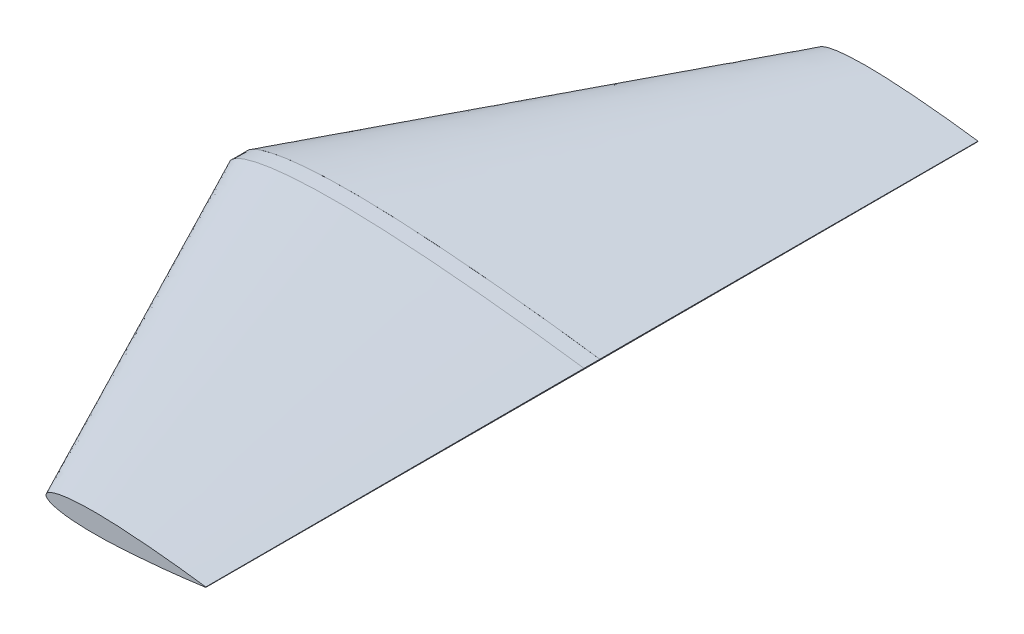
SolidWorks part; units mm, degrees
ref_plane "Front Plane" through (0, 0, 0) normal (0, 0, 1) x (1, 0, 0)
ref_plane "Top Plane" through (0, 0, 0) normal (0, 1, 0) x (1, 0, 0)
ref_plane "Right Plane" through (0, 0, 0) normal (1, 0, 0) x (0, 0, -1)
curve "Curve4"
  spline degree 3 poles (358.4, 0.4516, 0) (358.3705, 0.4558, 0) (358.2526, 0.4725, 0) (357.9874, 0.509, 0) (357.546, 0.5715, 0) (356.9284, 0.6576, 0) (356.1355, 0.7678, 0) (355.168, 0.9029, 0) (354.0268, 1.0605, 0) (352.7131, 1.2421, 0) (351.2282, 1.4459, 0) (349.5733, 1.6714, 0) (347.7504, 1.9192, 0) (345.7612, 2.1875, 0) (343.6077, 2.4759, 0) (341.2918, 2.7836, 0) (338.816, 3.1105, 0) (336.1826, 3.4545, 0) (333.3945, 3.8164, 0) (330.454, 4.1932, 0) (327.3643, 4.5866, 0) (324.1284, 4.9933, 0) (320.7495, 5.4142, 0) (317.231, 5.8471, 0) (313.5761, 6.2924, 0) (309.7885, 6.747, 0) (305.8722, 7.2123, 0) (301.8309, 7.6858, 0) (297.6686, 8.1675, 0) (293.3892, 8.6552, 0) (288.9974, 9.1496, 0) (284.497, 9.6477, 0) (279.8927, 10.1501, 0) (275.1891, 10.6553, 0) (270.3907, 11.1619, 0) (265.5024, 11.6693, 0) (260.5288, 12.1761, 0) (255.4751, 12.6823, 0) (250.346, 13.1852, 0) (245.1467, 13.6846, 0) (239.8823, 14.1796, 0) (234.5581, 14.668, 0) (229.1793, 15.1508, 0) (223.7512, 15.6241, 0) (218.2791, 16.0891, 0) (212.7683, 16.5431, 0) (207.2245, 16.9852, 0) (201.6529, 17.4146, 0) (196.0593, 17.8296, 0) (190.4489, 18.2291, 0) (184.8275, 18.6126, 0) (179.2006, 18.9767, 0) (173.5737, 19.3225, 0) (167.9523, 19.6472, 0) (162.3419, 19.9501, 0) (156.7482, 20.2303, 0) (151.1766, 20.4854, 0) (145.6328, 20.7154, 0) (140.1219, 20.9183, 0) (134.6497, 21.094, 0) (129.2216, 21.2398, 0) (123.8427, 21.3564, 0) (118.5184, 21.4415, 0) (113.2539, 21.4948, 0) (108.0545, 21.5157, 0) (102.9253, 21.5027, 0) (97.8714, 21.4558, 0) (92.8977, 21.3741, 0) (88.0093, 21.2574, 0) (83.2107, 21.1052, 0) (78.5069, 20.9172, 0) (73.9023, 20.6935, 0) (69.4018, 20.4334, 0) (65.0095, 20.1377, 0) (60.73, 19.8061, 0) (56.5673, 19.4392, 0) (52.5257, 19.0369, 0) (48.6089, 18.6007, 0) (44.821, 18.1299, 0) (41.1656, 17.6258, 0) (37.6465, 17.0894, 0) (34.2671, 16.5208, 0) (31.0305, 15.9218, 0) (27.9401, 15.2926, 0) (24.9987, 14.635, 0) (22.2095, 13.9494, 0) (19.5749, 13.2371, 0) (17.0977, 12.4992, 0) (14.7801, 11.737, 0) (12.6247, 10.9513, 0) (10.6329, 10.1436, 0) (8.807, 9.3144, 0) (7.1485, 8.4651, 0) (5.6585, 7.5971, 0) (4.3394, 6.7094, 0) (3.1907, 5.8047, 0) (2.2147, 4.8816, 0) (1.4118, 3.9406, 0) (0.7832, 2.9815, 0) (0.332, 2.0033, 0) (0.0601, 1.0072, 0) (-0.0298, 0, 0) (0.0601, -1.0072, 0) (0.332, -2.0033, 0) (0.7832, -2.9815, 0) (1.4118, -3.9406, 0) (2.2147, -4.8816, 0) (3.1907, -5.8047, 0) (4.3394, -6.7094, 0) (5.6585, -7.5971, 0) (7.1485, -8.4651, 0) (8.807, -9.3144, 0) (10.6329, -10.1436, 0) (12.6247, -10.9513, 0) (14.7801, -11.737, 0) (17.0977, -12.4992, 0) (19.5749, -13.2371, 0) (22.2095, -13.9494, 0) (24.9987, -14.635, 0) (27.9401, -15.2926, 0) (31.0305, -15.9218, 0) (34.2671, -16.5208, 0) (37.6465, -17.0894, 0) (41.1656, -17.6258, 0) (44.821, -18.1299, 0) (48.6089, -18.6007, 0) (52.5257, -19.0369, 0) (56.5673, -19.4392, 0) (60.73, -19.8061, 0) (65.0095, -20.1377, 0) (69.4018, -20.4334, 0) (73.9023, -20.6935, 0) (78.5069, -20.9172, 0) (83.2107, -21.1052, 0) (88.0093, -21.2574, 0) (92.8977, -21.3741, 0) (97.8714, -21.4558, 0) (102.9253, -21.5027, 0) (108.0545, -21.5157, 0) (113.2539, -21.4948, 0) (118.5184, -21.4415, 0) (123.8427, -21.3564, 0) (129.2216, -21.2398, 0) (134.6497, -21.094, 0) (140.1219, -20.9183, 0) (145.6328, -20.7154, 0) (151.1766, -20.4854, 0) (156.7482, -20.2303, 0) (162.3419, -19.9501, 0) (167.9523, -19.6472, 0) (173.5737, -19.3225, 0) (179.2006, -18.9767, 0) (184.8275, -18.6126, 0) (190.4489, -18.2291, 0) (196.0593, -17.8296, 0) (201.6529, -17.4146, 0) (207.2245, -16.9852, 0) (212.7683, -16.5431, 0) (218.2791, -16.0891, 0) (223.7512, -15.6241, 0) (229.1793, -15.1508, 0) (234.5581, -14.668, 0) (239.8823, -14.1796, 0) (245.1467, -13.6846, 0) (250.346, -13.1852, 0) (255.4751, -12.6823, 0) (260.5288, -12.1761, 0) (265.5024, -11.6693, 0) (270.3907, -11.1619, 0) (275.1891, -10.6553, 0) (279.8927, -10.1501, 0) (284.497, -9.6477, 0) (288.9974, -9.1496, 0) (293.3892, -8.6552, 0) (297.6686, -8.1675, 0) (301.8309, -7.6858, 0) (305.8722, -7.2123, 0) (309.7885, -6.747, 0) (313.5761, -6.2924, 0) (317.231, -5.8471, 0) (320.7495, -5.4142, 0) (324.1284, -4.9933, 0) (327.3643, -4.5866, 0) (330.454, -4.1932, 0) (333.3945, -3.8164, 0) (336.1826, -3.4545, 0) (338.816, -3.1105, 0) (341.2918, -2.7836, 0) (343.6077, -2.4759, 0) (345.7612, -2.1875, 0) (347.7504, -1.9192, 0) (349.5733, -1.6714, 0) (351.2282, -1.4459, 0) (352.7131, -1.2421, 0) (354.0268, -1.0605, 0) (355.168, -0.9029, 0) (356.1355, -0.7678, 0) (356.9284, -0.6576, 0) (357.546, -0.5715, 0) (357.9874, -0.509, 0) (358.2526, -0.4725, 0) (358.3705, -0.4558, 0) (358.4, -0.4516, 0) knots 0 0 0 0 0.000122 0.000489 0.001099 0.001952 0.003048 0.004385 0.005962 0.007777 0.009829 0.012115 0.014633 0.01738 0.020354 0.023551 0.02697 0.030605 0.034453 0.03851 0.042773 0.047237 0.051897 0.05675 0.061789 0.067011 0.072409 0.077978 0.083713 0.089608 0.095657 0.101854 0.108194 0.114669 0.121273 0.127999 0.134842 0.141793 0.148847 0.155997 0.163234 0.170552 0.177943 0.185401 0.192918 0.200486 0.208098 0.215746 0.223423 0.231122 0.238834 0.246551 0.254267 0.261974 0.269664 0.27733 0.284963 0.292558 0.300106 0.307599 0.315032 0.322395 0.329684 0.336889 0.344006 0.351026 0.357943 0.364751 0.371444 0.378015 0.384458 0.390767 0.396937 0.402962 0.408837 0.414556 0.420115 0.425508 0.430733 0.435783 0.440655 0.445344 0.449849 0.454165 0.458289 0.462219 0.465954 0.469491 0.472828 0.475967 0.478906 0.481648 0.484196 0.486552 0.488722 0.490717 0.492547 0.494228 0.495783 0.497239 0.498632 0.5 0.501368 0.502761 0.504217 0.505772 0.507453 0.509283 0.511278 0.513448 0.515804 0.518352 0.521094 0.524033 0.527172 0.530509 0.534046 0.537781 0.541711 0.545835 0.550151 0.554656 0.559345 0.564217 0.569267 0.574492 0.579885 0.585444 0.591163 0.597038 0.603063 0.609233 0.615542 0.621985 0.628556 0.635249 0.642057 0.648974 0.655994 0.663111 0.670316 0.677605 0.684968 0.692401 0.699894 0.707442 0.715037 0.72267 0.730336 0.738026 0.745733 0.753449 0.761166 0.768878 0.776577 0.784254 0.791902 0.799514 0.807082 0.814599 0.822057 0.829448 0.836766 0.844003 0.851153 0.858207 0.865158 0.872001 0.878727 0.885331 0.891806 0.898146 0.904343 0.910392 0.916287 0.922022 0.927591 0.932989 0.938211 0.94325 0.948103 0.952763 0.957227 0.96149 0.965547 0.969395 0.97303 0.976449 0.979646 0.98262 0.985367 0.987885 0.990171 0.992223 0.994038 0.995615 0.996952 0.998048 0.998901 0.999511 0.999878 1 1 1 1
sketch "Sketch2" plane through (0, 0, 0) normal (0, 0, 1) x (1, 0, 0)
  line L0 (358.4, 0.4516) -> (358.4, -0.4516)
  spline S0 degree 3 poles (958.0339, 3953.6087) (386.4418, -11.6955) (372.8591, -1.5368) (357.9874, 0.509) (357.546, 0.5715) (356.9284, 0.6576) (356.1355, 0.7678) (355.168, 0.9029) (354.0268, 1.0605) (352.7131, 1.2421) (351.2282, 1.4459) (349.5733, 1.6714) (347.7504, 1.9192) (345.7612, 2.1875) (343.6077, 2.4759) (341.2918, 2.7836) (338.816, 3.1105) (336.1826, 3.4545) (333.3945, 3.8164) (330.454, 4.1932) (327.3643, 4.5866) (324.1284, 4.9933) (320.7495, 5.4142) (317.231, 5.8471) (313.5761, 6.2924) (309.7885, 6.747) (305.8722, 7.2123) (301.8309, 7.6858) (297.6686, 8.1675) (293.3892, 8.6552) (288.9974, 9.1496) (284.497, 9.6477) (279.8927, 10.1501) (275.1891, 10.6553) (270.3907, 11.1619) (265.5024, 11.6693) (260.5288, 12.1761) (255.4751, 12.6823) (250.346, 13.1852) (245.1467, 13.6846) (239.8823, 14.1796) (234.5581, 14.668) (229.1793, 15.1508) (223.7512, 15.6241) (218.2791, 16.0891) (212.7683, 16.5431) (207.2245, 16.9852) (201.6529, 17.4146) (196.0593, 17.8296) (190.4489, 18.2291) (184.8275, 18.6126) (179.2006, 18.9767) (173.5737, 19.3225) (167.9523, 19.6472) (162.3419, 19.9501) (156.7482, 20.2303) (151.1766, 20.4854) (145.6328, 20.7154) (140.1219, 20.9183) (134.6497, 21.094) (129.2216, 21.2398) (123.8427, 21.3564) (118.5184, 21.4415) (113.2539, 21.4948) (108.0545, 21.5157) (102.9253, 21.5027) (97.8714, 21.4558) (92.8977, 21.3741) (88.0093, 21.2574) (83.2107, 21.1052) (78.5069, 20.9172) (73.9023, 20.6935) (69.4018, 20.4334) (65.0095, 20.1377) (60.73, 19.8061) (56.5673, 19.4392) (52.5257, 19.0369) (48.6089, 18.6007) (44.821, 18.1299) (41.1656, 17.6258) (37.6465, 17.0894) (34.2671, 16.5208) (31.0305, 15.9218) (27.9401, 15.2926) (24.9987, 14.635) (22.2095, 13.9494) (19.5749, 13.2371) (17.0977, 12.4992) (14.7801, 11.737) (12.6247, 10.9513) (10.6329, 10.1436) (8.807, 9.3144) (7.1485, 8.4651) (5.6585, 7.5971) (4.3394, 6.7094) (3.1907, 5.8047) (2.2147, 4.8816) (1.4118, 3.9406) (0.7832, 2.9815) (0.332, 2.0033) (0.0601, 1.0072) (-0.0298, 0) (0.0601, -1.0072) (0.332, -2.0033) (0.7832, -2.9815) (1.4118, -3.9406) (2.2147, -4.8816) (3.1907, -5.8047) (4.3394, -6.7094) (5.6585, -7.5971) (7.1485, -8.4651) (8.807, -9.3144) (10.6329, -10.1436) (12.6247, -10.9513) (14.7801, -11.737) (17.0977, -12.4992) (19.5749, -13.2371) (22.2095, -13.9494) (24.9987, -14.635) (27.9401, -15.2926) (31.0305, -15.9218) (34.2671, -16.5208) (37.6465, -17.0894) (41.1656, -17.6258) (44.821, -18.1299) (48.6089, -18.6007) (52.5257, -19.0369) (56.5673, -19.4392) (60.73, -19.8061) (65.0095, -20.1377) (69.4018, -20.4334) (73.9023, -20.6935) (78.5069, -20.9172) (83.2107, -21.1052) (88.0093, -21.2574) (92.8977, -21.3741) (97.8714, -21.4558) (102.9253, -21.5027) (108.0545, -21.5157) (113.2539, -21.4948) (118.5184, -21.4415) (123.8427, -21.3564) (129.2216, -21.2398) (134.6497, -21.094) (140.1219, -20.9183) (145.6328, -20.7154) (151.1766, -20.4854) (156.7482, -20.2303) (162.3419, -19.9501) (167.9523, -19.6472) (173.5737, -19.3225) (179.2006, -18.9767) (184.8275, -18.6126) (190.4489, -18.2291) (196.0593, -17.8296) (201.6529, -17.4146) (207.2245, -16.9852) (212.7683, -16.5431) (218.2791, -16.0891) (223.7512, -15.6241) (229.1793, -15.1508) (234.5581, -14.668) (239.8823, -14.1796) (245.1467, -13.6846) (250.346, -13.1852) (255.4751, -12.6823) (260.5288, -12.1761) (265.5024, -11.6693) (270.3907, -11.1619) (275.1891, -10.6553) (279.8927, -10.1501) (284.497, -9.6477) (288.9974, -9.1496) (293.3892, -8.6552) (297.6686, -8.1675) (301.8309, -7.6858) (305.8722, -7.2123) (309.7885, -6.747) (313.5761, -6.2924) (317.231, -5.8471) (320.7495, -5.4142) (324.1284, -4.9933) (327.3643, -4.5866) (330.454, -4.1932) (333.3945, -3.8164) (336.1826, -3.4545) (338.816, -3.1105) (341.2918, -2.7836) (343.6077, -2.4759) (345.7612, -2.1875) (347.7504, -1.9192) (349.5733, -1.6714) (351.2282, -1.4459) (352.7131, -1.2421) (354.0268, -1.0605) (355.168, -0.9029) (356.1355, -0.7678) (356.9284, -0.6576) (357.546, -0.5715) (357.9874, -0.509) (372.8587, 1.5367) (386.441, 11.6949) (957.9815, -3953.2445) knots -0.060521 -0.060521 -0.060521 -0.060521 0.000122 0.000489 0.001099 0.001952 0.003048 0.004385 0.005962 0.007777 0.009829 0.012115 0.014633 0.01738 0.020354 0.023551 0.02697 0.030605 0.034453 0.03851 0.042773 0.047237 0.051897 0.05675 0.061789 0.067011 0.072409 0.077978 0.083713 0.089608 0.095657 0.101854 0.108194 0.114669 0.121273 0.127999 0.134842 0.141793 0.148847 0.155997 0.163234 0.170552 0.177943 0.185401 0.192918 0.200486 0.208098 0.215746 0.223423 0.231122 0.238834 0.246551 0.254267 0.261974 0.269664 0.27733 0.284963 0.292558 0.300106 0.307599 0.315032 0.322395 0.329684 0.336889 0.344006 0.351026 0.357943 0.364751 0.371444 0.378015 0.384458 0.390767 0.396937 0.402962 0.408837 0.414556 0.420115 0.425508 0.430733 0.435783 0.440655 0.445344 0.449849 0.454165 0.458289 0.462219 0.465954 0.469491 0.472828 0.475967 0.478906 0.481648 0.484196 0.486552 0.488722 0.490717 0.492547 0.494228 0.495783 0.497239 0.498632 0.5 0.501368 0.502761 0.504217 0.505772 0.507453 0.509283 0.511278 0.513448 0.515804 0.518352 0.521094 0.524033 0.527172 0.530509 0.534046 0.537781 0.541711 0.545835 0.550151 0.554656 0.559345 0.564217 0.569267 0.574492 0.579885 0.585444 0.591163 0.597038 0.603063 0.609233 0.615542 0.621985 0.628556 0.635249 0.642057 0.648974 0.655994 0.663111 0.670316 0.677605 0.684968 0.692401 0.699894 0.707442 0.715037 0.72267 0.730336 0.738026 0.745733 0.753449 0.761166 0.768878 0.776577 0.784254 0.791902 0.799514 0.807082 0.814599 0.822057 0.829448 0.836766 0.844003 0.851153 0.858207 0.865158 0.872001 0.878727 0.885331 0.891806 0.898146 0.904343 0.910392 0.916287 0.922022 0.927591 0.932989 0.938211 0.94325 0.948103 0.952763 0.957227 0.96149 0.965547 0.969395 0.97303 0.976449 0.979646 0.98262 0.985367 0.987885 0.990171 0.992223 0.994038 0.995615 0.996952 0.998048 0.998901 0.999511 0.999878 1.060519 1.060519 1.060519 1.060519 only from (358.4, 0.4516) to (358.4, -0.4516) construction
  spline S1 degree 3 poles (358.4, 0.4516) (358.3705, 0.4558) (358.2526, 0.4725) (357.9874, 0.509) (357.546, 0.5715) (356.9284, 0.6576) (356.1355, 0.7678) (355.168, 0.9029) (354.0268, 1.0605) (352.7131, 1.2421) (351.2282, 1.4459) (349.5733, 1.6714) (347.7504, 1.9192) (345.7612, 2.1875) (343.6077, 2.4759) (341.2918, 2.7836) (338.816, 3.1105) (336.1826, 3.4545) (333.3945, 3.8164) (330.454, 4.1932) (327.3643, 4.5866) (324.1284, 4.9933) (320.7495, 5.4142) (317.231, 5.8471) (313.5761, 6.2924) (309.7885, 6.747) (305.8722, 7.2123) (301.8309, 7.6858) (297.6686, 8.1675) (293.3892, 8.6552) (288.9974, 9.1496) (284.497, 9.6477) (279.8927, 10.1501) (275.1891, 10.6553) (270.3907, 11.1619) (265.5024, 11.6693) (260.5288, 12.1761) (255.4751, 12.6823) (250.346, 13.1852) (245.1467, 13.6846) (239.8823, 14.1796) (234.5581, 14.668) (229.1793, 15.1508) (223.7512, 15.6241) (218.2791, 16.0891) (212.7683, 16.5431) (207.2245, 16.9852) (201.6529, 17.4146) (196.0593, 17.8296) (190.4489, 18.2291) (184.8275, 18.6126) (179.2006, 18.9767) (173.5737, 19.3225) (167.9523, 19.6472) (162.3419, 19.9501) (156.7482, 20.2303) (151.1766, 20.4854) (145.6328, 20.7154) (140.1219, 20.9183) (134.6497, 21.094) (129.2216, 21.2398) (123.8427, 21.3564) (118.5184, 21.4415) (113.2539, 21.4948) (108.0545, 21.5157) (102.9253, 21.5027) (97.8714, 21.4558) (92.8977, 21.3741) (88.0093, 21.2574) (83.2107, 21.1052) (78.5069, 20.9172) (73.9023, 20.6935) (69.4018, 20.4334) (65.0095, 20.1377) (60.73, 19.8061) (56.5673, 19.4392) (52.5257, 19.0369) (48.6089, 18.6007) (44.821, 18.1299) (41.1656, 17.6258) (37.6465, 17.0894) (34.2671, 16.5208) (31.0305, 15.9218) (27.9401, 15.2926) (24.9987, 14.635) (22.2095, 13.9494) (19.5749, 13.2371) (17.0977, 12.4992) (14.7801, 11.737) (12.6247, 10.9513) (10.6329, 10.1436) (8.807, 9.3144) (7.1485, 8.4651) (5.6585, 7.5971) (4.3394, 6.7094) (3.1907, 5.8047) (2.2147, 4.8816) (1.4118, 3.9406) (0.7832, 2.9815) (0.332, 2.0033) (0.0601, 1.0072) (-0.0298, 0) (0.0601, -1.0072) (0.332, -2.0033) (0.7832, -2.9815) (1.4118, -3.9406) (2.2147, -4.8816) (3.1907, -5.8047) (4.3394, -6.7094) (5.6585, -7.5971) (7.1485, -8.4651) (8.807, -9.3144) (10.6329, -10.1436) (12.6247, -10.9513) (14.7801, -11.737) (17.0977, -12.4992) (19.5749, -13.2371) (22.2095, -13.9494) (24.9987, -14.635) (27.9401, -15.2926) (31.0305, -15.9218) (34.2671, -16.5208) (37.6465, -17.0894) (41.1656, -17.6258) (44.821, -18.1299) (48.6089, -18.6007) (52.5257, -19.0369) (56.5673, -19.4392) (60.73, -19.8061) (65.0095, -20.1377) (69.4018, -20.4334) (73.9023, -20.6935) (78.5069, -20.9172) (83.2107, -21.1052) (88.0093, -21.2574) (92.8977, -21.3741) (97.8714, -21.4558) (102.9253, -21.5027) (108.0545, -21.5157) (113.2539, -21.4948) (118.5184, -21.4415) (123.8427, -21.3564) (129.2216, -21.2398) (134.6497, -21.094) (140.1219, -20.9183) (145.6328, -20.7154) (151.1766, -20.4854) (156.7482, -20.2303) (162.3419, -19.9501) (167.9523, -19.6472) (173.5737, -19.3225) (179.2006, -18.9767) (184.8275, -18.6126) (190.4489, -18.2291) (196.0593, -17.8296) (201.6529, -17.4146) (207.2245, -16.9852) (212.7683, -16.5431) (218.2791, -16.0891) (223.7512, -15.6241) (229.1793, -15.1508) (234.5581, -14.668) (239.8823, -14.1796) (245.1467, -13.6846) (250.346, -13.1852) (255.4751, -12.6823) (260.5288, -12.1761) (265.5024, -11.6693) (270.3907, -11.1619) (275.1891, -10.6553) (279.8927, -10.1501) (284.497, -9.6477) (288.9974, -9.1496) (293.3892, -8.6552) (297.6686, -8.1675) (301.8309, -7.6858) (305.8722, -7.2123) (309.7885, -6.747) (313.5761, -6.2924) (317.231, -5.8471) (320.7495, -5.4142) (324.1284, -4.9933) (327.3643, -4.5866) (330.454, -4.1932) (333.3945, -3.8164) (336.1826, -3.4545) (338.816, -3.1105) (341.2918, -2.7836) (343.6077, -2.4759) (345.7612, -2.1875) (347.7504, -1.9192) (349.5733, -1.6714) (351.2282, -1.4459) (352.7131, -1.2421) (354.0268, -1.0605) (355.168, -0.9029) (356.1355, -0.7678) (356.9284, -0.6576) (357.546, -0.5715) (357.9874, -0.509) (358.2526, -0.4725) (358.3705, -0.4558) (358.4, -0.4516) knots 0 0 0 0 0.000122 0.000489 0.001099 0.001952 0.003048 0.004385 0.005962 0.007777 0.009829 0.012115 0.014633 0.01738 0.020354 0.023551 0.02697 0.030605 0.034453 0.03851 0.042773 0.047237 0.051897 0.05675 0.061789 0.067011 0.072409 0.077978 0.083713 0.089608 0.095657 0.101854 0.108194 0.114669 0.121273 0.127999 0.134842 0.141793 0.148847 0.155997 0.163234 0.170552 0.177943 0.185401 0.192918 0.200486 0.208098 0.215746 0.223423 0.231122 0.238834 0.246551 0.254267 0.261974 0.269664 0.27733 0.284963 0.292558 0.300106 0.307599 0.315032 0.322395 0.329684 0.336889 0.344006 0.351026 0.357943 0.364751 0.371444 0.378015 0.384458 0.390767 0.396937 0.402962 0.408837 0.414556 0.420115 0.425508 0.430733 0.435783 0.440655 0.445344 0.449849 0.454165 0.458289 0.462219 0.465954 0.469491 0.472828 0.475967 0.478906 0.481648 0.484196 0.486552 0.488722 0.490717 0.492547 0.494228 0.495783 0.497239 0.498632 0.5 0.501368 0.502761 0.504217 0.505772 0.507453 0.509283 0.511278 0.513448 0.515804 0.518352 0.521094 0.524033 0.527172 0.530509 0.534046 0.537781 0.541711 0.545835 0.550151 0.554656 0.559345 0.564217 0.569267 0.574492 0.579885 0.585444 0.591163 0.597038 0.603063 0.609233 0.615542 0.621985 0.628556 0.635249 0.642057 0.648974 0.655994 0.663111 0.670316 0.677605 0.684968 0.692401 0.699894 0.707442 0.715037 0.72267 0.730336 0.738026 0.745733 0.753449 0.761166 0.768878 0.776577 0.784254 0.791902 0.799514 0.807082 0.814599 0.822057 0.829448 0.836766 0.844003 0.851153 0.858207 0.865158 0.872001 0.878727 0.885331 0.891806 0.898146 0.904343 0.910392 0.916287 0.922022 0.927591 0.932989 0.938211 0.94325 0.948103 0.952763 0.957227 0.96149 0.965547 0.969395 0.97303 0.976449 0.979646 0.98262 0.985367 0.987885 0.990171 0.992223 0.994038 0.995615 0.996952 0.998048 0.998901 0.999511 0.999878 1 1 1 1
  point P2 (358.4, 0)
ref_plane "Plane1" through (0, 0, 382.02) normal (0, 0, 1) x (1, 0, 0)
curve "Curve6"
  spline degree 3 poles (161, 0.2, 0) (160.9167, 0.2136, 0) (160.5878, 0.2674, 0) (159.8459, 0.3582, 0) (158.6167, 0.5336, 0) (156.9044, 0.7747, 0) (154.7197, 1.0579, 0) (152.0808, 1.4127, 0) (149, 1.8068, 0) (145.495, 2.263, 0) (141.5867, 2.7335, 0) (137.3047, 3.2584, 0) (132.6749, 3.797, 0) (127.7205, 4.3416, 0) (122.4781, 4.9135, 0) (116.9751, 5.4844, 0) (111.2473, 6.0363, 0) (105.3289, 6.6051, 0) (99.2544, 7.1256, 0) (93.0685, 7.6401, 0) (86.8052, 8.1104, 0) (80.5015, 8.5276, 0) (74.1982, 8.8988, 0) (67.9348, 9.2091, 0) (61.7481, 9.4549, 0) (55.674, 9.6008, 0) (49.7536, 9.6736, 0) (44.0259, 9.6622, 0) (38.5218, 9.5268, 0) (33.277, 9.3152, 0) (28.3219, 8.9982, 0) (23.6896, 8.584, 0) (19.4031, 8.0712, 0) (15.4933, 7.4578, 0) (11.9838, 6.7608, 0) (8.8904, 6.0144, 0) (6.2467, 5.1543, 0) (4.043, 4.2646, 0) (2.2931, 3.3144, 0) (1.0207, 2.2893, 0) (0.197, 1.1962, 0) (-0.0922, 0, 0) (0.197, -1.1962, 0) (1.0207, -2.2893, 0) (2.2931, -3.3144, 0) (4.043, -4.2646, 0) (6.2467, -5.1543, 0) (8.8904, -6.0144, 0) (11.9838, -6.7608, 0) (15.4933, -7.4578, 0) (19.4031, -8.0712, 0) (23.6896, -8.584, 0) (28.3219, -8.9982, 0) (33.277, -9.3152, 0) (38.5218, -9.5268, 0) (44.0259, -9.6622, 0) (49.7536, -9.6736, 0) (55.674, -9.6008, 0) (61.7481, -9.4549, 0) (67.9348, -9.2091, 0) (74.1982, -8.8988, 0) (80.5015, -8.5276, 0) (86.8052, -8.1104, 0) (93.0685, -7.6401, 0) (99.2544, -7.1256, 0) (105.3289, -6.6051, 0) (111.2473, -6.0363, 0) (116.9751, -5.4844, 0) (122.4781, -4.9135, 0) (127.7205, -4.3416, 0) (132.6749, -3.797, 0) (137.3047, -3.2584, 0) (141.5867, -2.7335, 0) (145.495, -2.263, 0) (149, -1.8068, 0) (152.0808, -1.4127, 0) (154.7197, -1.0579, 0) (156.9044, -0.7747, 0) (158.6167, -0.5336, 0) (159.8459, -0.3582, 0) (160.5878, -0.2674, 0) (160.9167, -0.2136, 0) (161, -0.2, 0) knots 0 0 0 0 0.000771 0.003046 0.006828 0.012119 0.018848 0.02696 0.036452 0.047231 0.059262 0.072425 0.086655 0.101857 0.117974 0.134848 0.152416 0.17056 0.189182 0.208132 0.227285 0.24658 0.265865 0.284988 0.303888 0.322445 0.340511 0.357996 0.374785 0.390822 0.405963 0.420155 0.433319 0.445408 0.456311 0.466012 0.47447 0.481694 0.487709 0.492596 0.496534 0.5 0.503466 0.507404 0.512291 0.518306 0.52553 0.533988 0.543689 0.554592 0.566681 0.579845 0.594037 0.609178 0.625215 0.642004 0.659489 0.677555 0.696112 0.715012 0.734135 0.75342 0.772715 0.791868 0.810818 0.82944 0.847584 0.865152 0.882026 0.898143 0.913345 0.927575 0.940738 0.952769 0.963548 0.97304 0.981152 0.987881 0.993172 0.996954 0.999229 1 1 1 1
sketch "Sketch3" plane through (0, 0, 0) normal (0, 0, 1) x (1, 0, 0)
  line L0 (161, 0.2) -> (161, -0.2)
  spline S0 degree 3 poles (485.6143, 1973.3383) (180.7866, -18.3284) (171.6884, -1.0915) (159.8459, 0.3582) (158.6167, 0.5336) (156.9044, 0.7747) (154.7197, 1.0579) (152.0808, 1.4127) (149, 1.8068) (145.495, 2.263) (141.5867, 2.7335) (137.3047, 3.2584) (132.6749, 3.797) (127.7205, 4.3416) (122.4781, 4.9135) (116.9751, 5.4844) (111.2473, 6.0363) (105.3289, 6.6051) (99.2544, 7.1256) (93.0685, 7.6401) (86.8052, 8.1104) (80.5015, 8.5276) (74.1982, 8.8988) (67.9348, 9.2091) (61.7481, 9.4549) (55.674, 9.6008) (49.7536, 9.6736) (44.0259, 9.6622) (38.5218, 9.5268) (33.277, 9.3152) (28.3219, 8.9982) (23.6896, 8.584) (19.4031, 8.0712) (15.4933, 7.4578) (11.9838, 6.7608) (8.8904, 6.0144) (6.2467, 5.1543) (4.043, 4.2646) (2.2931, 3.3144) (1.0207, 2.2893) (0.197, 1.1962) (-0.0922, 0) (0.197, -1.1962) (1.0207, -2.2893) (2.2931, -3.3144) (4.043, -4.2646) (6.2467, -5.1543) (8.8904, -6.0144) (11.9838, -6.7608) (15.4933, -7.4578) (19.4031, -8.0712) (23.6896, -8.584) (28.3219, -8.9982) (33.277, -9.3152) (38.5218, -9.5268) (44.0259, -9.6622) (49.7536, -9.6736) (55.674, -9.6008) (61.7481, -9.4549) (67.9348, -9.2091) (74.1982, -8.8988) (80.5015, -8.5276) (86.8052, -8.1104) (93.0685, -7.6401) (99.2544, -7.1256) (105.3289, -6.6051) (111.2473, -6.0363) (116.9751, -5.4844) (122.4781, -4.9135) (127.7205, -4.3416) (132.6749, -3.797) (137.3047, -3.2584) (141.5867, -2.7335) (145.495, -2.263) (149, -1.8068) (152.0808, -1.4127) (154.7197, -1.0579) (156.9044, -0.7747) (158.6167, -0.5336) (159.8459, -0.3582) (171.6881, 1.0915) (180.7861, 18.3274) (485.5887, -1973.1705) knots -0.102179 -0.102179 -0.102179 -0.102179 0.000771 0.003046 0.006828 0.012119 0.018848 0.02696 0.036452 0.047231 0.059262 0.072425 0.086655 0.101857 0.117974 0.134848 0.152416 0.17056 0.189182 0.208132 0.227285 0.24658 0.265865 0.284988 0.303888 0.322445 0.340511 0.357996 0.374785 0.390822 0.405963 0.420155 0.433319 0.445408 0.456311 0.466012 0.47447 0.481694 0.487709 0.492596 0.496534 0.5 0.503466 0.507404 0.512291 0.518306 0.52553 0.533988 0.543689 0.554592 0.566681 0.579845 0.594037 0.609178 0.625215 0.642004 0.659489 0.677555 0.696112 0.715012 0.734135 0.75342 0.772715 0.791868 0.810818 0.82944 0.847584 0.865152 0.882026 0.898143 0.913345 0.927575 0.940738 0.952769 0.963548 0.97304 0.981152 0.987881 0.993172 0.996954 0.999229 1.102176 1.102176 1.102176 1.102176 only from (161, 0.2) to (161, -0.2) construction
  spline S1 degree 3 poles (161, 0.2) (160.9167, 0.2136) (160.5878, 0.2674) (159.8459, 0.3582) (158.6167, 0.5336) (156.9044, 0.7747) (154.7197, 1.0579) (152.0808, 1.4127) (149, 1.8068) (145.495, 2.263) (141.5867, 2.7335) (137.3047, 3.2584) (132.6749, 3.797) (127.7205, 4.3416) (122.4781, 4.9135) (116.9751, 5.4844) (111.2473, 6.0363) (105.3289, 6.6051) (99.2544, 7.1256) (93.0685, 7.6401) (86.8052, 8.1104) (80.5015, 8.5276) (74.1982, 8.8988) (67.9348, 9.2091) (61.7481, 9.4549) (55.674, 9.6008) (49.7536, 9.6736) (44.0259, 9.6622) (38.5218, 9.5268) (33.277, 9.3152) (28.3219, 8.9982) (23.6896, 8.584) (19.4031, 8.0712) (15.4933, 7.4578) (11.9838, 6.7608) (8.8904, 6.0144) (6.2467, 5.1543) (4.043, 4.2646) (2.2931, 3.3144) (1.0207, 2.2893) (0.197, 1.1962) (-0.0922, 0) (0.197, -1.1962) (1.0207, -2.2893) (2.2931, -3.3144) (4.043, -4.2646) (6.2467, -5.1543) (8.8904, -6.0144) (11.9838, -6.7608) (15.4933, -7.4578) (19.4031, -8.0712) (23.6896, -8.584) (28.3219, -8.9982) (33.277, -9.3152) (38.5218, -9.5268) (44.0259, -9.6622) (49.7536, -9.6736) (55.674, -9.6008) (61.7481, -9.4549) (67.9348, -9.2091) (74.1982, -8.8988) (80.5015, -8.5276) (86.8052, -8.1104) (93.0685, -7.6401) (99.2544, -7.1256) (105.3289, -6.6051) (111.2473, -6.0363) (116.9751, -5.4844) (122.4781, -4.9135) (127.7205, -4.3416) (132.6749, -3.797) (137.3047, -3.2584) (141.5867, -2.7335) (145.495, -2.263) (149, -1.8068) (152.0808, -1.4127) (154.7197, -1.0579) (156.9044, -0.7747) (158.6167, -0.5336) (159.8459, -0.3582) (160.5878, -0.2674) (160.9167, -0.2136) (161, -0.2) knots 0 0 0 0 0.000771 0.003046 0.006828 0.012119 0.018848 0.02696 0.036452 0.047231 0.059262 0.072425 0.086655 0.101857 0.117974 0.134848 0.152416 0.17056 0.189182 0.208132 0.227285 0.24658 0.265865 0.284988 0.303888 0.322445 0.340511 0.357996 0.374785 0.390822 0.405963 0.420155 0.433319 0.445408 0.456311 0.466012 0.47447 0.481694 0.487709 0.492596 0.496534 0.5 0.503466 0.507404 0.512291 0.518306 0.52553 0.533988 0.543689 0.554592 0.566681 0.579845 0.594037 0.609178 0.625215 0.642004 0.659489 0.677555 0.696112 0.715012 0.734135 0.75342 0.772715 0.791868 0.810818 0.82944 0.847584 0.865152 0.882026 0.898143 0.913345 0.927575 0.940738 0.952769 0.963548 0.97304 0.981152 0.987881 0.993172 0.996954 0.999229 1 1 1 1
sketch "Sketch4" plane through (0, 0, 382.02) normal (0, 0, 1) x (1, 0, 0)
  line L0 (358.4, 0.2005) -> (358.4, -0.2005)
  spline S1 degree 3 poles (358.4, 0.2005) (358.3165, 0.2142) (357.9867, 0.2681) (357.243, 0.3591) (356.0106, 0.535) (354.2939, 0.7767) (352.1036, 1.0606) (349.4579, 1.4163) (346.3693, 1.8115) (342.8552, 2.2688) (338.9369, 2.7405) (334.644, 3.2668) (330.0023, 3.8068) (325.0353, 4.3527) (319.7794, 4.9261) (314.2623, 5.4985) (308.5198, 6.0517) (302.5863, 6.622) (296.4961, 7.1438) (290.2944, 7.6597) (284.0151, 8.1312) (277.6952, 8.5494) (271.3758, 8.9216) (265.0963, 9.2327) (258.8938, 9.4791) (252.8041, 9.6254) (246.8685, 9.6983) (241.1261, 9.687) (235.6079, 9.5512) (230.3497, 9.3391) (225.3819, 9.0213) (220.7378, 8.606) (216.4402, 8.0918) (212.5205, 7.4769) (209.002, 6.7781) (205.9006, 6.0298) (203.2501, 5.1675) (201.0408, 4.2755) (199.2864, 3.3229) (198.0108, 2.2952) (197.1849, 1.1993) (196.895, 0) (197.1849, -1.1993) (198.0108, -2.2952) (199.2864, -3.3229) (201.0408, -4.2755) (203.2501, -5.1675) (205.9006, -6.0298) (209.002, -6.7781) (212.5205, -7.4769) (216.4402, -8.0918) (220.7378, -8.606) (225.3819, -9.0213) (230.3497, -9.3391) (235.6079, -9.5512) (241.1261, -9.687) (246.8685, -9.6983) (252.8041, -9.6254) (258.8938, -9.4791) (265.0963, -9.2327) (271.3758, -8.9216) (277.6952, -8.5494) (284.0151, -8.1312) (290.2944, -7.6597) (296.4961, -7.1438) (302.5863, -6.622) (308.5198, -6.0517) (314.2623, -5.4985) (319.7794, -4.9261) (325.0353, -4.3527) (330.0023, -3.8068) (334.644, -3.2668) (338.9369, -2.7405) (342.8552, -2.2688) (346.3693, -1.8115) (349.4579, -1.4163) (352.1036, -1.0606) (354.2939, -0.7767) (356.0106, -0.535) (357.243, -0.3591) (357.9867, -0.2681) (358.3165, -0.2142) (358.4, -0.2005) knots 0 0 0 0 0.000771 0.003046 0.006828 0.012119 0.018848 0.02696 0.036452 0.047231 0.059262 0.072425 0.086655 0.101857 0.117974 0.134848 0.152416 0.17056 0.189182 0.208132 0.227285 0.24658 0.265865 0.284988 0.303888 0.322445 0.340511 0.357996 0.374785 0.390822 0.405963 0.420155 0.433319 0.445408 0.456311 0.466012 0.47447 0.481694 0.487709 0.492596 0.496534 0.5 0.503466 0.507404 0.512291 0.518306 0.52553 0.533988 0.543689 0.554592 0.566681 0.579845 0.594037 0.609178 0.625215 0.642004 0.659489 0.677555 0.696112 0.715012 0.734135 0.75342 0.772715 0.791868 0.810818 0.82944 0.847584 0.865152 0.882026 0.898143 0.913345 0.927575 0.940738 0.952769 0.963548 0.97304 0.981152 0.987881 0.993172 0.996954 0.999229 1 1 1 1
  point P2 (358.4, 0)
  point P7 (196.9874, 0)
sketch "Sketch7" plane through (0, 0, 0) normal (0, 1, 0) x (1, 0, 0)
  line L0 (358.4, -382.02) -> (358.4, 0)
loft "Loft1" add profiles "Sketch2", "Sketch4" connector at (358.4, 0.4516, 0) connector at (358.4, 0.2005, 382.02)
extrude "Boss-Extrude3" add sketch "Sketch2<2>" against normal blind 15.96 separate body
sketch "Sketch2<2>" plane through (0, 0, 0) normal (0, 0, 1) x (1, 0, 0) same geometry as "Sketch2"
ref_plane "Plane4" through (0, 0, -7.98) normal (0, 0, 1) x (1, 0, 0)
mirror "Mirror12" about plane through (0, 0, -7.98) normal (0, 0, 1) of bodies 103
sketch "Wing Geometry Sketch" plane through (0, 0, 0) normal (0, 1, 0) x (1, 0, 0)
  line L0 (196.9874, 397.98) -> (0, 15.96) construction
  line L1 (196.9874, 397.98) -> (358.4, 397.98) construction
  line L2 (358.4, 397.98) -> (358.4, 15.96) construction
  line L5 (358.4, 15.96) -> (0, 15.96) construction
  line L6 (358.4, 182.9186) -> (86.0917, 182.9186) construction
  line L7 (154.1687, 182.9186) -> (154.1687, 7.98)
  line L8 (358.4, 15.96) -> (358.4, 0) construction
  line L9 (358.4, 15.96) -> (0, 15.96) construction
  line L10 (358.4, 397.98) -> (358.4, 15.96) construction
  line L11 (358.4, 7.98) -> (0, 7.98) construction
  line L13 (196.9874, 397.98) -> (0, 15.96) construction
  point P13 (154.1687, 182.9186)
  dimension "D1" = 272.3083
  dimension "D2" = 68.0771
